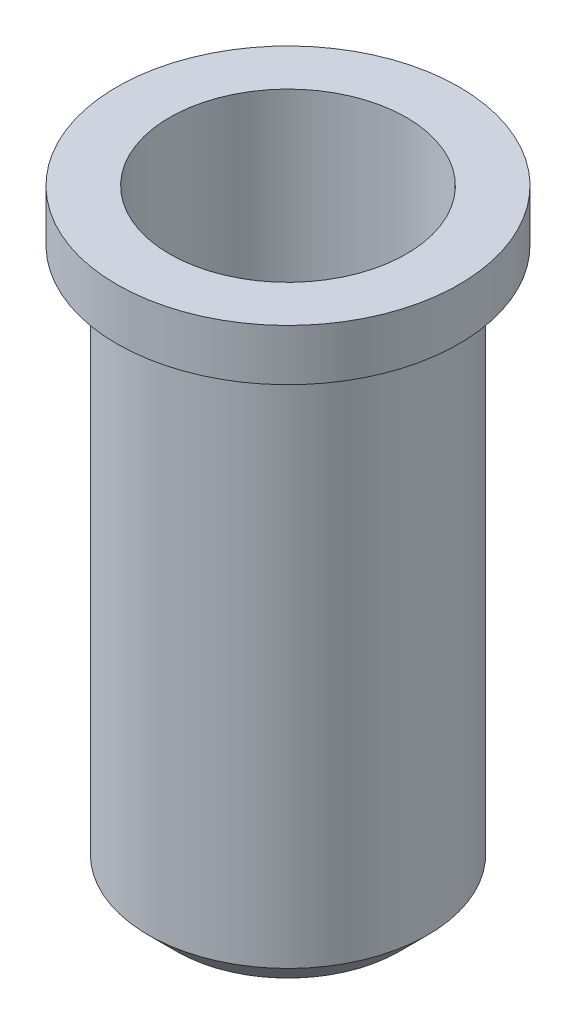
SolidWorks part; units mm, degrees
ref_plane "Front Plane" through (0, 0, 0) normal (0, 0, 1) x (1, 0, 0)
ref_plane "Top Plane" through (0, 0, 0) normal (0, 1, 0) x (1, 0, 0)
ref_plane "Right Plane" through (0, 0, 0) normal (1, 0, 0) x (0, 0, -1)
sketch "Sketch1" plane through (0, 0, 0) normal (0, 0, 1) x (1, 0, 0)
  line L0 (0, 0) -> (0, 8.4047) construction
  line L1 (0, 0) -> (0.9906, 0)
  line L2 (0, 0) -> (0, 0.254)
  line L4 (1.2446, 0.254) -> (1.2446, 4.953)
  line L8 (1.0541, 5.4102) -> (1.0541, 0.8382)
  line L9 (1.0541, 5.4102) -> (1.524, 5.4102)
  line L10 (1.0541, 5.4102) -> (1.0541, 7.9798)
  line L11 (1.2446, 4.953) -> (1.524, 4.953)
  line L12 (1.524, 5.4102) -> (1.524, 4.953)
  line L13 (1.2446, 0.254) -> (0.9906, 0)
  line L14 (1.0541, 0.8382) -> (0, 0.254)
  dimension "D1" = 0.4572
  dimension "D2" = 1.524
  dimension "D3" = 5.4102
  dimension "D4" = 1.2446
  dimension "D5" = 0.254
  dimension "D6" = 0.254
  dimension "D7" = 4.572
  dimension "D8" = 0.1905
  dimension "D9" = 0.254
revolve "Revolve1" add sketch "Sketch1" angle 360 about L0 region at (0.0562, 0.127, 0)
